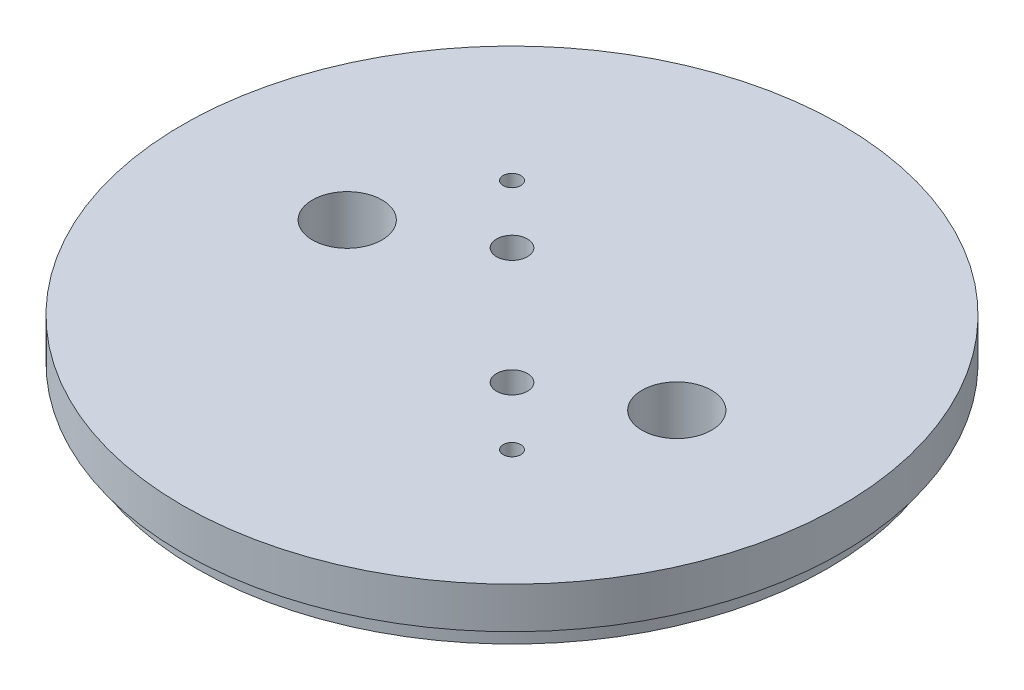
SolidWorks part; units mm, degrees
material "6061-T4 (SS)"
ref_plane "Front Plane" through (0, 0, 0) normal (0, 0, 1) x (1, 0, 0)
ref_plane "Top Plane" through (0, 0, 0) normal (0, 1, 0) x (1, 0, 0)
ref_plane "Right Plane" through (0, 0, 0) normal (1, 0, 0) x (0, 0, -1)
sketch "Sketch1" plane through (0, 0, 0) normal (0, 1, 0) x (1, 0, 0)
  line L0 (0, -50.8) -> (0, 50.8) construction
  line L1 (-50.8, 0) -> (50.8, 0) construction
  line L2 (-17.9605, 17.9605) -> (0, 0) construction
  line L3 (0, 56.7387) -> (0, 29.6936) construction
  line L4 (3.6407, 56.7387) -> (3.6407, 29.6936) construction
  line L5 (-3.6407, 56.7387) -> (-3.6407, 29.6936) construction
  line L6 (0, -56.7387) -> (0, -29.6936) construction
  line L7 (3.6407, -56.7387) -> (3.6407, -29.6936) construction
  line L8 (-3.6407, -56.7387) -> (-3.6407, -29.6936) construction
  line L9 (-35.921, -35.921) -> (54.3236, 54.3236) construction
  circle A0 centre (0, 0) radius 50.8
  circle A1 centre (0, 0) radius 3.175 construction
  circle A2 centre (25.4, 0) radius 5.3578
  circle A3 centre (-25.4, 0) radius 5.3578
  circle A4 centre (-17.9605, 17.9605) radius 1.3589
  arc A6 (3.6407, 56.7387) -> (-3.6407, 56.7387) centre (0, 56.7387) ccw construction
  arc A7 (-3.6407, 29.6936) -> (3.6407, 29.6936) centre (0, 29.6936) ccw construction
  arc A8 (3.6407, -56.7387) -> (-3.6407, -56.7387) centre (0, -56.7387) cw construction
  arc A9 (-3.6407, -29.6936) -> (3.6407, -29.6936) centre (0, -29.6936) cw construction
  circle A10 centre (17.9605, -17.9605) radius 1.3589
  circle A11 centre (-8.9803, 8.9803) radius 2.3813
  circle A12 centre (8.9803, -8.9803) radius 2.3813
  point P16 (0, 43.2162)
  point P19 (0, 0)
  point P26 (0, -43.2162)
  dimension "D1" = 101.6
  dimension "D2" = 6.35
  dimension "D3" = 10.7156
  dimension "D5" = 2.7178
  dimension "D8" = 4.7625
  dimension "D6" = 25.4
  dimension "D7" = 45
  dimension "D4" = 45
  dimension "D9" = 25.4
extrude "Boss-Extrude1" add sketch "Sketch1" along normal blind 9.525
sketch "Sketch2" plane through (0, 0, 0) normal (0, -1, 0) x (1, 0, 0)
  circle A0 centre (0, 0) radius 50.8
  circle A1 centre (0, 0) radius 48.641
  dimension "D1" = 101.6
  dimension "D2" = 97.282
extrude "Cut-Extrude1" cut sketch "Sketch2" against normal blind 3.175
sketch "Sketch3" plane through (0, 9.525, 0) normal (0, 1, 0) x (1, 0, 0)
  line L0 (0, 50.8) -> (0, -50.8) construction
  line L1 (-50.8, 0) -> (50.8, 0) construction
  line L2 (0, 34.798) -> (0, 13.97) construction
  line L3 (3.2385, 34.798) -> (3.2385, 13.97)
  line L4 (-3.2385, 34.798) -> (-3.2385, 13.97)
  line L5 (0, -34.798) -> (0, -13.97) construction
  line L6 (3.2385, -34.798) -> (3.2385, -13.97)
  line L7 (-3.2385, -34.798) -> (-3.2385, -13.97)
  circle A0 centre (0, 0) radius 50.8 construction
  arc A1 (3.2385, 34.798) -> (-3.2385, 34.798) centre (0, 34.798) ccw
  arc A2 (-3.2385, 13.97) -> (3.2385, 13.97) centre (0, 13.97) ccw
  arc A3 (3.2385, -34.798) -> (-3.2385, -34.798) centre (0, -34.798) cw
  arc A4 (-3.2385, -13.97) -> (3.2385, -13.97) centre (0, -13.97) cw
  point P7 (0, 13.97)
  point P8 (0, 34.798)
  point P12 (0, 24.384)
  point P20 (0, -24.384)
  point P25 (0, -34.798)
  point P26 (0, -13.97)
  dimension "D1" = 13.97
  dimension "D2" = 20.828
  dimension "D3" = 6.477
extrude "Cut-Extrude2" cut sketch "Sketch3" against normal blind 3.556 from offset 5.969 offset against normal yes
equation "\"Lead_Screw_Dist\" = 2in"
equation "\"Coupler_OD\" = 3.899in"
equation "\"Coupler_ID\" = 3.755in"
equation "\"Lead_Screw_Hole_Diam\" = (27/64)*1in"
equation "\"D3@Sketch1\"=\"Lead_Screw_Hole_Diam\""
equation "\"D9@Sketch1\"=\"Lead_Screw_Dist\"/2"
